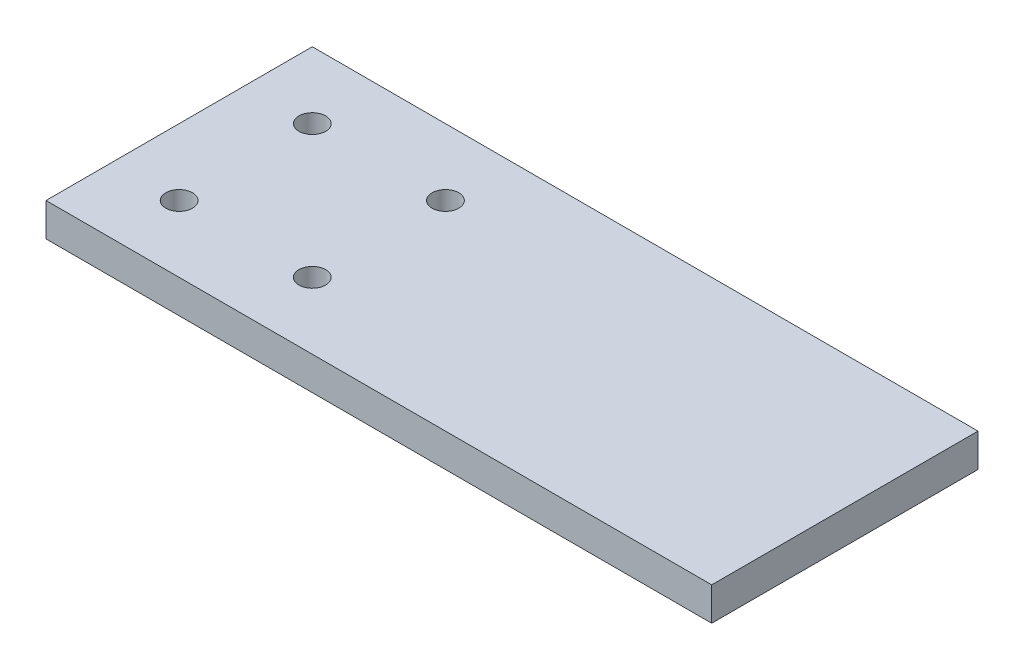
SolidWorks part; units mm, degrees
ref_plane "Front Plane" through (0, 0, 0) normal (0, 0, 1) x (1, 0, 0)
ref_plane "Top Plane" through (0, 0, 0) normal (0, 1, 0) x (1, 0, 0)
ref_plane "Right Plane" through (0, 0, 0) normal (1, 0, 0) x (0, 0, -1)
sketch "Sketch1" plane through (0, 0, 0) normal (0, 1, 0) x (1, 0, 0)
  line L0 (50.8, 25.4) -> (76.2, 25.4)
  line L1 (-50.8, -25.4) -> (50.8, -25.4)
  line L2 (-50.8, -25.4) -> (-50.8, 25.4)
  line L3 (-50.8, 25.4) -> (50.8, 25.4)
  line L5 (-50.8, -25.4) -> (50.8, 25.4) construction
  line L6 (-50.8, 25.4) -> (50.8, -25.4) construction
  line L7 (76.2, 25.4) -> (76.2, -25.4)
  line L8 (76.2, -25.4) -> (50.8, -25.4)
  point P0 (0, 0)
  dimension "D1" = 101.6
  dimension "D2" = 50.8
  dimension "D3" = 25.4
extrude "Boss-Extrude1" add sketch "Sketch1" along normal blind 6.35
sketch "Sketch2" plane through (0, 6.35, 0) normal (0, 1, 0) x (1, 0, 0)
  line L4 (76.2, 25.4) -> (-50.8, 25.4) construction
  line L5 (-50.8, -25.4) -> (76.2, -25.4) construction
  line L7 (0, 25.4) -> (0, -25.4) construction
  line L8 (-50.8, 25.4) -> (-50.8, -25.4) construction
  dimension "D1" = 50.8
hole_wizard "#10 Clearance Hole1" positions "Sketch3" profile "Sketch4" hole size "#10" standard "ANSI Inch" end condition through all
sketch "Sketch3" plane through (0, 6.35, 0) normal (0, 1, 0) x (1, 0, 0)
  line L4 (-38.1, 25.4) -> (-38.1, -25.4) construction
  line L5 (76.2, 25.4) -> (-50.8, 25.4) construction
  line L6 (-50.8, -25.4) -> (76.2, -25.4) construction
  line L8 (-12.7, 25.4) -> (-12.7, -25.4) construction
  line L9 (-50.8, 25.4) -> (-50.8, -25.4) construction
  line L11 (-50.8, 12.7) -> (0, 12.7) construction
  line L13 (-50.8, -12.7) -> (0, -12.7) construction
  point P0 (-38.1, 12.7)
  point P2 (-12.7, 12.7)
  point P4 (-12.7, -12.7)
  point P6 (-38.1, -12.7)
  dimension "D1" = 12.7
  dimension "D2" = 38.1
  dimension "D3" = 12.7
  dimension "D4" = 12.7
  dimension "D5" = 50.8
  dimension "D6" = 50.8
sketch "Sketch4" plane through (-38.1, 6.35, -12.7) normal (1, 0, 0) x (0, 0, 1)
  line L0 (0, 0) -> (0, 6.35)
  line L1 (0, 6.35) -> (2.5527, 6.35)
  line L2 (2.5527, 6.35) -> (2.5527, 0)
  line L5 (2.5527, 0) -> (0, 0)
  line L11 (0, -6.35) -> (0, 107.95) construction
  dimension "Thru Hole Dia." = 5.1054
  dimension "Thru Hole Depth" = 6.35
sketch "Sketch5" plane through (0, 6.35, 0) normal (0, 1, 0) x (1, 0, 0)
  line L0 (76.2, 0) -> (19.05, 0) construction
  line L1 (76.2, -25.4) -> (76.2, 25.4) construction
  dimension "D1" = 57.15
